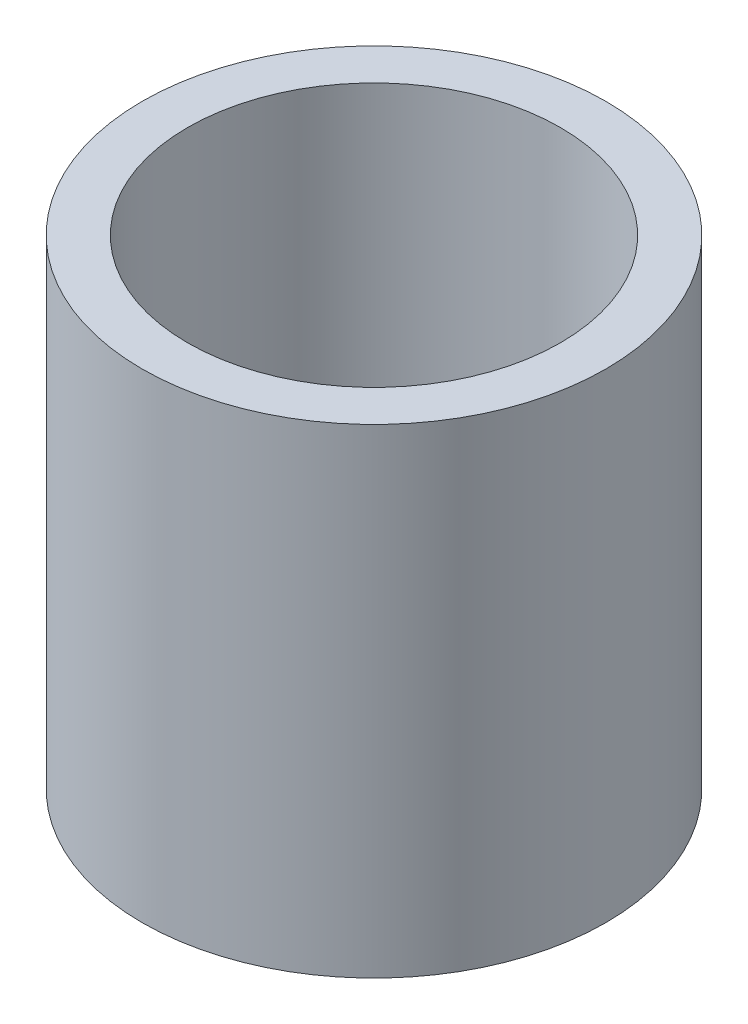
SolidWorks part; units mm, degrees
ref_plane "Front Plane" through (0, 0, 0) normal (0, 0, 1) x (1, 0, 0)
ref_plane "Top Plane" through (0, 0, 0) normal (0, 1, 0) x (1, 0, 0)
ref_plane "Right Plane" through (0, 0, 0) normal (1, 0, 0) x (0, 0, -1)
sketch "Sketch1" plane through (0, 0, 0) normal (0, 1, 0) x (1, 0, 0)
  circle A0 centre (0, 0) radius 27.5
  dimension "SLEEVE_OD" = 55
extrude "Boss-Extrude1" add sketch "Sketch1" along normal blind 56.8774
sketch "Sketch2" plane through (0, 0, 0) normal (0, 1, 0) x (1, 0, 0)
  circle A0 centre (0, 0) radius 22.1179
  dimension "BORE_D" = 44.2359
extrude "Cut-Extrude1" cut sketch "Sketch2" along normal through all
chamfer "Chamfer1" distance 3.6162 angle 61.626 rebuild error yes
